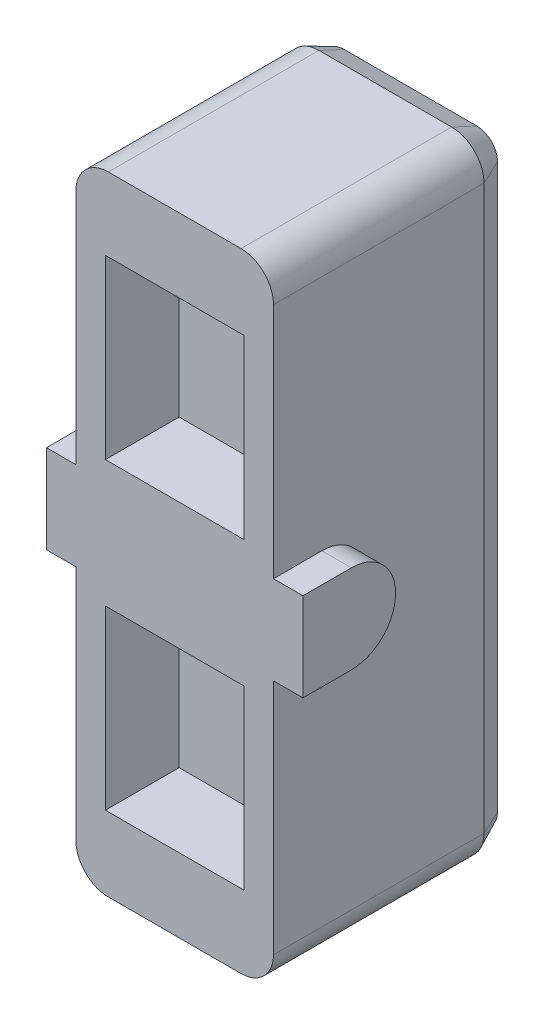
SolidWorks part; units mm, degrees
ref_plane "Plan de face" through (0, 0, 0) normal (0, 0, 1) x (1, 0, 0)
ref_plane "Plan de dessus" through (0, 0, 0) normal (0, 1, 0) x (1, 0, 0)
ref_plane "Plan de droite" through (0, 0, 0) normal (1, 0, 0) x (0, 0, -1)
sketch "Esquisse2" plane through (0, 0, 0) normal (0, 0, 1) x (1, 0, 0)
  line L1 (1.1, 0) -> (5.6, 0)
  line L2 (0, 1.1) -> (0, 20.2)
  line L3 (1.1, 21.3) -> (5.6, 21.3)
  line L4 (6.7, 1.1) -> (6.7, 20.2)
  arc A0 (5.6, 21.3) -> (6.7, 20.2) centre (5.6, 20.2) cw
  arc A1 (5.6, 0) -> (6.7, 1.1) centre (5.6, 1.1) ccw
  arc A2 (1.1, 0) -> (0, 1.1) centre (1.1, 1.1) cw
  arc A3 (0, 20.2) -> (1.1, 21.3) centre (1.1, 20.2) cw
  point P7 (6.7, 21.3)
  point P12 (0, 0)
  point P15 (0, 21.3)
  dimension "D3" = 1.1
  dimension "D1" = 6.7
  dimension "D2" = 21.3
extrude "Boss.-Extru.1" add sketch "Esquisse2" along normal blind 8
sketch "Esquisse3" plane through (0, 0, 8) normal (0, 0, 1) x (1, 0, 0)
  line L0 (0, 20.2) -> (0, 1.1) construction
  line L1 (1, 18.8) -> (5.7, 18.8)
  line L2 (1, 18.8) -> (1, 12.8)
  line L3 (1, 12.8) -> (5.7, 12.8)
  line L4 (5.7, 18.8) -> (5.7, 12.8)
  line L5 (6.7, 1.1) -> (6.7, 20.2) construction
  line L6 (5.6, 21.3) -> (1.1, 21.3) construction
  line L8 (1.1, 0) -> (5.6, 0) construction
  line L9 (1, 8.5) -> (5.7, 8.5)
  line L10 (1, 8.5) -> (1, 2.5)
  line L11 (1, 2.5) -> (5.7, 2.5)
  line L12 (5.7, 8.5) -> (5.7, 2.5)
  line L13 (-7.1761, 15.8) -> (15.2275, 15.8) construction
  dimension "D2" = 6
  dimension "D3" = 1
  dimension "D4" = 1
  dimension "D5" = 2.5
  dimension "D6" = 6
  dimension "D8" = 1
  dimension "D9" = 2.5
  dimension "D10" = 5.5
  dimension "D11" = 1
chamfer "Chanfrein1" distance 0.4 angle 65 8 edges at (3.35, 0, 0) (6.3778, 0.3222, 0) (0.3222, 0.3222, 0) (6.7, 10.65, 0) (0, 10.65, 0) (6.3778, 20.9778, 0) (0.3222, 20.9778, 0) (3.35, 21.3, 0) first distance on face at (3.35, 10.65, 0)
sketch "Esquisse5" plane through (0, 0, 0) normal (0, 0, 1) x (1, 0, 0)
  line L1 (1.54, 5.9) -> (5.1595, 5.9)
  line L2 (5.1595, 5.9) -> (3.3498, 1.9)
  line L3 (3.3498, 1.9) -> (1.54, 5.9)
  line L4 (3.3498, 3.3556) -> (2.47, 5.3)
  line L5 (2.47, 5.3) -> (4.2295, 5.3)
  line L6 (4.2295, 5.3) -> (3.3498, 3.3556)
  line L7 (5.6, 0.4) -> (1.1, 0.4) construction
  line L8 (1.54, 15.4) -> (5.16, 15.4)
  line L9 (5.16, 15.4) -> (3.35, 19.4)
  line L10 (3.35, 19.4) -> (1.54, 15.4)
  line L11 (2.4701, 16) -> (4.2299, 16)
  line L12 (4.2299, 16) -> (3.35, 17.9446)
  line L13 (3.35, 17.9446) -> (2.4701, 16)
  line L14 (1.1, 20.9) -> (5.6, 20.9) construction
  line L15 (0.4, 1.1) -> (0.4, 20.2) construction
  line L16 (6.3, 20.2) -> (6.3, 1.1) construction
  line L17 (6.3, 9.6541) -> (0.4, 9.6541) construction
  text T0 "<b>RNG</b>" font "Century Gothic" height 2.5
  dimension "D1" = 0.6
  dimension "D2" = 0.6
  dimension "D3" = 0.6
  dimension "D4" = 1.8098
  dimension "D5" = 1.8097
  dimension "D6" = 4
  dimension "D7" = 1.5
  dimension "D8" = 0.6
  dimension "D9" = 0.6
  dimension "D10" = 0.6
  dimension "D11" = 4
  dimension "D12" = 1.81
  dimension "D13" = 1.81
  dimension "D14" = 1.5
  dimension "D15" = 1.14
  dimension "D16" = 1.1405
  dimension "D17" = 1.14
extrude "Boss.-Extru.2" add sketch "Esquisse5<4>" against normal blind 0.2
sketch "Esquisse5<4>" plane through (0, 0, 0) normal (0, 0, 1) x (1, 0, 0) same geometry as "Esquisse5"
extrude "Enlèv. mat.-Extru.3" cut sketch "Esquisse5" along normal blind 0.2
extrude "Enlèv. mat.-Extru.4" cut sketch "Esquisse3" against normal blind 2.5
sketch "Esquisse6" plane through (0, 0, 0) normal (-1, 0, 0) x (0, 0, 1)
  line L0 (-8.8899, 10.65) -> (18.0179, 10.65) construction
  line L1 (8, 20.2) -> (0.8578, 20.2) construction
  line L2 (8, 1.1) -> (0.8578, 1.1) construction
  line L3 (0.8578, 20.2) -> (0.8578, 1.1) construction
  line L5 (6.3578, 12.15) -> (8, 12.15)
  line L6 (8, 1.1) -> (8, 20.2) construction
  line L7 (8, 12.15) -> (8, 9.15)
  line L8 (8, 9.15) -> (6.3578, 9.15)
  arc A0 (6.3578, 9.15) -> (6.3578, 12.15) centre (6.3578, 10.65) cw
  dimension "D4" = 1.5
  dimension "D1" = 9.55
  dimension "D2" = 9.55
  dimension "D3" = 0
  dimension "D5" = 5.5
extrude "Boss.-Extru.3" add sketch "Esquisse6" along normal blind 1 and the other way blind 7.7
